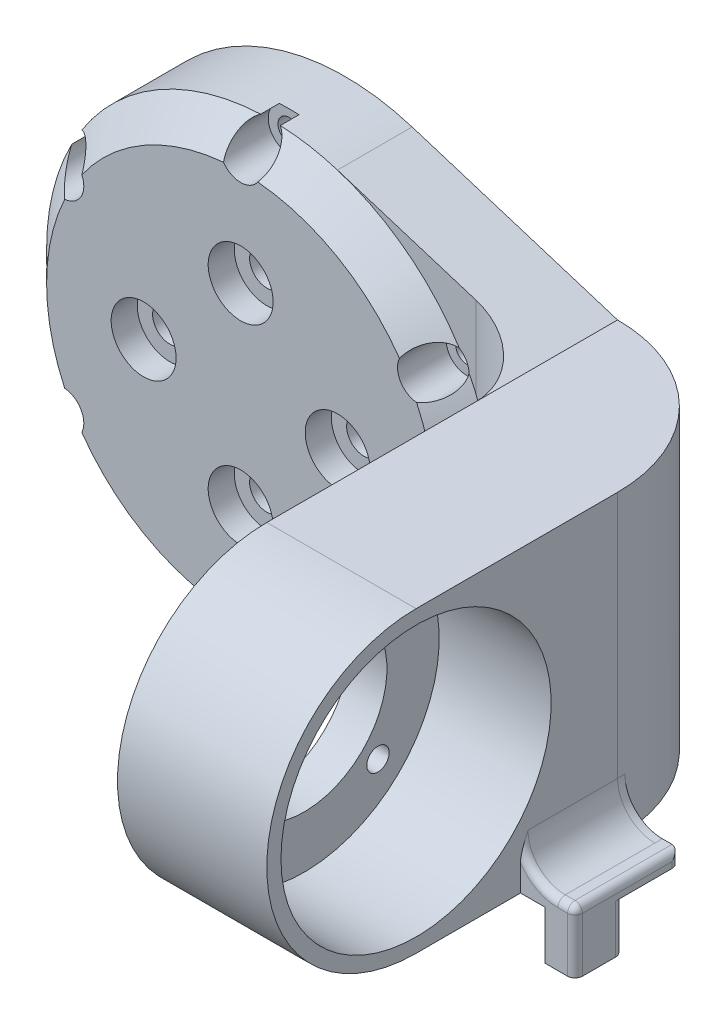
SolidWorks part; units mm, degrees
ref_plane "Piano frontale" through (0, 0, 0) normal (0, 0, 1) x (1, 0, 0)
ref_plane "Piano superiore" through (0, 0, 0) normal (0, 1, 0) x (1, 0, 0)
ref_plane "Piano destro" through (0, 0, 0) normal (1, 0, 0) x (0, 0, -1)
sketch "Schizzo1" plane through (0, 0, 0) normal (0, 0, 1) x (1, 0, 0)
  circle A0 centre (0, 0) radius 30
  circle A1 centre (0, 0) radius 27.5 construction
  circle A2 centre (0, 0) radius 21
  dimension "D1" = 55
  dimension "D2" = 60
  dimension "D3" = 42
extrude "Estrusione-Estrusione1" add sketch "Schizzo1" along normal blind 5
sketch "Schizzo7" plane through (0, 0, 5) normal (0, 0, 1) x (1, 0, 0)
  circle A0 centre (0, 0) radius 30
  circle A1 centre (0, 0) radius 30 construction
extrude "Estrusione-Estrusione2" add sketch "Schizzo7" along normal blind 5
sketch "Schizzo3" plane through (0, 0, 0) normal (0, 0, 1) x (1, 0, 0)
  circle A0 centre (0, 27.5) radius 1.5
  circle A1 centre (0, 0) radius 27.5 construction
  dimension "D1" = 55
  dimension "D2" = 3
extrude "Taglio-Estrusione3" cut sketch "Schizzo3" along normal blind 8
sketch "Schizzo10" plane through (0, 0, 10) normal (0, 0, 1) x (1, 0, 0)
  circle A0 centre (0, 27.5) radius 1.5
  circle A1 centre (0, 27.5) radius 1.5 construction
  circle A2 centre (0, 27.5) radius 2.8
  dimension "D1" = 5.6
extrude "Taglio-Estrusione4" cut sketch "Schizzo10" against normal blind 2.5 contours A2
pattern_circular "RipetizioneCircolare1" count 6 over 360 about axis through (0, 0, 0) along (0, 0, 1) of "Taglio-Estrusione3", "Taglio-Estrusione4"
sketch "Schizzo12" plane through (0, 0, 0) normal (-1, 0, 0) x (0, 0, 1)
  line L1 (0, 0) -> (47, 0) construction
  circle A0 centre (47, 0) radius 20
  circle A1 centre (47, 0) radius 18.1
  dimension "D1" = 36.2
  dimension "D3" = 40
  dimension "D2" = 47
extrude "Estrusione-Estrusione5" add sketch "Schizzo12" along direction (1, 0, 0) on the side of the normal blind 1 and the other way blind 14 from offset 42.5 offset against normal yes
sketch "Schizzo13" plane through (41.5, 0, 0) normal (-1, 0, 0) x (0, 0, 1)
  circle A0 centre (47, 0) radius 11.1
  circle A1 centre (47, 0) radius 20
  circle A2 centre (47, 0) radius 20 construction
  dimension "D1" = 22.2
extrude "Estrusione-Estrusione6" add sketch "Schizzo13" along normal blind 5
sketch "Schizzo14" plane through (36.5, 0, 0) normal (-1, 0, 0) x (0, 0, 1)
  line L2 (47, 0) -> (61, 0) construction
  circle A0 centre (56.8995, 9.8995) radius 1.5
  circle A1 centre (47, 0) radius 14
  circle A2 centre (47, 0) radius 11.1 construction
  dimension "D2" = 3
  dimension "D3" = 28
  dimension "D1" = 45
extrude "Taglio-Estrusione5" cut sketch "Schizzo14" along direction (-1, 0, 0) on the side against the normal through all contours A0 A1 | A1 A0
pattern_circular "RipetizioneCircolare2" count 4 over 360 about axis through (0, 0, 47) along (1, 0, 0) of "Taglio-Estrusione5"
sketch "Schizzo40" plane through (0, 0, 0) normal (0, 0, 1) x (1, 0, 0)
  line L0 (36.5, 20) -> (8.9714, 28.6271)
  line L3 (36.5, -20) -> (8.9714, -28.6271)
  line L5 (41.5, 20) -> (36.5, 20) construction
  line L6 (36.5, -20) -> (41.5, -20) construction
  line L7 (41.5, -20) -> (56.5, -20) construction
  line L8 (36.5, 20) -> (56.5, 20)
  line L10 (36.5, -20) -> (56.5, -20)
  line L11 (56.5, 20) -> (56.5, -20)
  line L12 (56.5, -20) -> (56.5, 20) construction
  circle A0 centre (0, 0) radius 30
  arc A1 (-1.3167, 29.9711) -> (-25.2974, 16.1258) centre (0, 0) ccw construction
extrude "Estrusione-Estrusione9" add sketch "Schizzo40" along normal blind 10
sketch "Schizzo42" plane through (0, 0, 10) normal (0, 0, 1) x (1, 0, 0)
  circle A0 centre (23.8157, 13.75) radius 2.8
  circle A1 centre (23.8157, -13.75) radius 2.8
  arc A2 (25.2974, 16.1258) -> (26.6141, 13.8452) centre (23.8157, 13.75) ccw construction
  arc A3 (26.6141, -13.8452) -> (25.2974, -16.1258) centre (23.8157, -13.75) ccw construction
extrude "Taglio-Estrusione6" cut sketch "Schizzo42" against normal up to surface (2.5 mm away) up to face at (25.3157, 13.75, 7.5)
sketch "Schizzo41" plane through (0, 0, 10) normal (0, 0, 1) x (1, 0, 0)
  line L1 (56.5, -20) -> (36.5, -20)
  line L2 (56.5, -20) -> (56.5, 20)
  line L3 (56.5, 20) -> (36.5, 20)
  line L4 (36.5, -20) -> (36.5, 20)
extrude "Estrusione-Estrusione10" add sketch "Schizzo41" along normal up to surface (37 mm away)
fillet "Raccordo3" radius 9 1 edges at (36.5, 0, 10)
fillet "Raccordo4" radius 20 1 edges at (56.5, 0, 0)
sketch "Schizzo43" plane through (0, -20, 0) normal (0, -1, 0) x (1, 0, 0)
  line L1 (43.5, 23) -> (46.7, 23)
  line L2 (43.5, 23) -> (43.5, 19)
  line L3 (43.5, 19) -> (46.7, 19)
  line L4 (46.7, 23) -> (46.7, 19)
  line L5 (53.1, 23) -> (56.3, 23)
  line L6 (53.1, 23) -> (53.1, 19)
  line L7 (53.1, 19) -> (56.3, 19)
  line L8 (56.3, 23) -> (56.3, 19)
  line L9 (59.8, 33) -> (63.8, 33)
  line L10 (59.8, 33) -> (59.8, 26.55)
  line L11 (59.8, 26.55) -> (63.8, 26.55)
  line L12 (63.8, 33) -> (63.8, 26.55)
  line L13 (36.5, 47) -> (36.5, 19) construction
  circle A0 centre (45.1, 26) radius 1.2
  circle A1 centre (54.7, 26) radius 1.2
  circle A2 centre (61.8, 29.775) radius 1.25
  circle A3 centre (45.1, 21) radius 1.25
  point P17 (45.1, 23)
  point P19 (54.7, 23)
  point P23 (63.8, 29.775)
  point P24 (61.8, 33)
  point P26 (46.7, 21)
  point P27 (45.1, 19)
  dimension "D1" = 2.4
  dimension "D2" = 2.4
  dimension "D8" = 2.5
  dimension "D9" = 2.5
  dimension "D3" = 4
  dimension "D4" = 0.55
  dimension "D5" = 4
  dimension "D6" = 3.2
  dimension "D7" = 3.2
  dimension "D11" = 6.4
  dimension "D12" = 3
  dimension "D13" = 7
  dimension "D14" = 3.5
  dimension "D15" = 6.45
extrude "Estrusione-Estrusione11" add sketch "Schizzo43" along normal blind 6.5
fillet "Raccordo7" radius 1 4 edges at (53.1, -23.25, 19) (43.5, -23.25, 19) (46.7, -23.25, 19) (56.3, -23.25, 19)
sketch "Schizzo44" plane through (0, -20, 0) normal (0, -1, 0) x (1, 0, 0)
  line L0 (63.8, 26.55) -> (63.8, 33) construction
  line L1 (36.5, 33) -> (63.8, 33)
  line L2 (36.5, 33) -> (36.5, 19)
  line L3 (36.5, 19) -> (63.8, 19)
  line L4 (63.8, 33) -> (63.8, 19)
  line L5 (54.1, 19) -> (55.3, 19) construction
  line L6 (63.8, 33) -> (59.8, 33) construction
  line L7 (36.5, 47) -> (36.5, 19) construction
extrude "Estrusione-Estrusione12" add sketch "Schizzo44" against normal blind 1.8
fillet "Raccordo10" radius 5 2 edges at (56.5, -18.2, 26.5) (56.4937, -18.2, 19.4998)
fillet "Raccordo11" radius 1 6 edges at (57.9645, -16.7355, 33) (62.65, -18.2, 33) (63.8, -19.1, 19) (63.8, -18.2, 26) (63.8, -23.25, 26.55) (63.8, -22.35, 33)
sketch "Schizzo46" plane through (36.5, 0, 0) normal (-1, 0, 0) x (0, 0, 1)
  line L0 (47, 0) -> (29.5059, -24.9841) construction
  line L1 (29.5059, -24.9841) -> (35.2417, -16.7926)
  line L2 (47, -20) -> (19, -20) construction
  line L3 (23.9728, -20) -> (42.5, -20)
  circle A0 centre (47, 0) radius 20.5
  circle A1 centre (47, 0) radius 30.5
  line M6 (19, -20) -> (47, -20)
  dimension "D1" = 61
  dimension "D2" = 41
  dimension "D3" = 55
extrude "Taglio-Estrusione8" cut sketch "Schizzo46" against normal blind 3.5 contours L1 A1 A0 M6
sketch "Schizzo47" plane through (0, 0, 5) normal (0, 0, -1) x (-1, 0, 0)
  circle A0 centre (0, 0) radius 13 construction
  circle A1 centre (13, 0) radius 2.3
  circle A2 centre (-13, 0) radius 2.3
  circle A3 centre (0, 13) radius 2.3
  circle A4 centre (0, -13) radius 2.3
  dimension "D1" = 26
  dimension "D2" = 4.6
extrude "Taglio-Estrusione9" cut sketch "Schizzo47" against normal blind 10
sketch "Schizzo48" plane through (0, 0, 5) normal (0, 0, -1) x (-1, 0, 0)
  circle A0 centre (0, 0) radius 16.25
  dimension "D1" = 32.5
extrude "Taglio-Estrusione10" cut sketch "Schizzo48" against normal blind 2
sketch "Schizzo49" plane through (0, 0, 10) normal (0, 0, 1) x (1, 0, 0)
  circle A0 centre (0, 0) radius 20
  circle A23 centre (0, 13) radius 2.3
  circle A24 centre (13, 0) radius 2.3
  circle A25 centre (0, -13) radius 2.3
  circle A26 centre (-13, 0) radius 2.3
  circle A27 centre (-13, 0) radius 2.3 construction
  circle A28 centre (0, 13) radius 2.3 construction
  circle A29 centre (13, 0) radius 2.3 construction
  circle A30 centre (0, -13) radius 2.3 construction
  dimension "D1" = 40
extrude "Estrusione-Estrusione13" add sketch "Schizzo49" along normal blind 4
chamfer "Smusso1" distance 10 angle 45 2 edges at (20, 0, 14) (20, 0, 10)
sketch "Schizzo50" plane through (0, 0, 14) normal (0, 0, 1) x (1, 0, 0)
  circle A0 centre (0, 13) radius 4.35
  circle A1 centre (-13, 0) radius 4.35
  circle A2 centre (13, 0) radius 4.35
  circle A3 centre (0, -13) radius 4.35
  dimension "D1" = 8.7
extrude "Taglio-Estrusione11" cut sketch "Schizzo50" against normal blind 3.5
